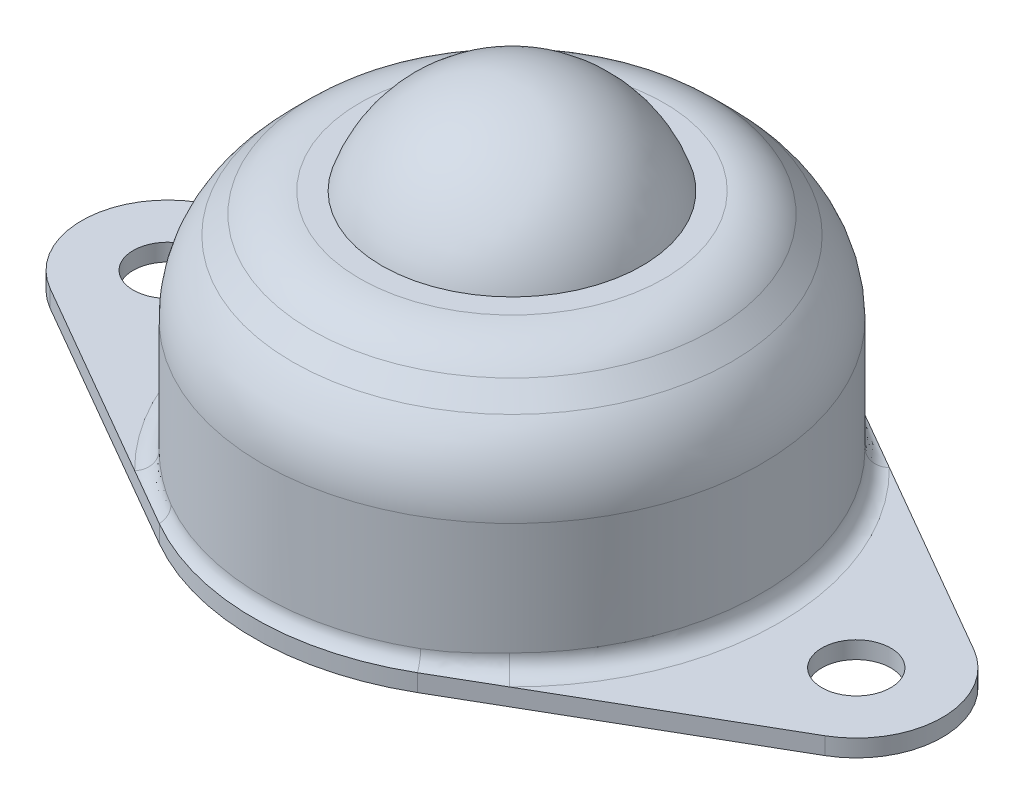
SolidWorks part; units mm, degrees
ref_plane "前视基准面" through (0, 0, 0) normal (0, 0, 1) x (1, 0, 0)
ref_plane "上视基准面" through (0, 0, 0) normal (0, 1, 0) x (1, 0, 0)
ref_plane "右视基准面" through (0, 0, 0) normal (1, 0, 0) x (0, 0, -1)
sketch "草图1" plane through (0, 0, 0) normal (0, 1, 0) x (1, 0, 0)
  line L0 (0, -26.7962) -> (0, 26.7962) construction
  line L1 (-22.5, 4.3301) -> (-7.5, 12.9904)
  line L2 (-22.5, -4.3301) -> (-7.5, -12.9904)
  line L3 (22.5, 4.3301) -> (7.5, 12.9904)
  line L4 (22.5, -4.3301) -> (7.5, -12.9904)
  circle A0 centre (0, 0) radius 15
  circle A1 centre (-20, 0) radius 2
  circle A2 centre (-20, 0) radius 5
  circle A3 centre (20, 0) radius 5
  circle A4 centre (20, 0) radius 2
  dimension "D1" = 4
  dimension "D3" = 30
  dimension "D4" = 10
  dimension "D2" = 20
extrude "凸台-拉伸1" add sketch "草图1" along normal blind 1 contours A2 A1 | A2 A0 L1 | A2 L2 A0 | A0 | A0 A3 L3 | L4 A3 A0 | A3 A4 region at (-15.4261, 0, -6.4178) region at (-17.5707, 0, -4.2077) region at (0, 0, 0) region at (-15.4261, 0, 6.4178) region at (15.4261, 0, -6.4178) region at (24.2077, 0, -2.4293) region at (15.4261, 0, 6.4178)
sketch "草图2" plane through (0, 1, 0) normal (0, 1, 0) x (1, 0, 0)
  circle A0 centre (0, 0) radius 14.5
  dimension "D1" = 29
extrude "凸台-拉伸2" add sketch "草图2" along normal blind 14
sketch "草图3" plane through (0, 0, 0) normal (0, 0, 1) x (1, 0, 0)
  line L0 (14.5, 15) -> (-14.5, 15) construction
  line L1 (0, 4.62) -> (0, 20.5)
  arc A0 (0, 20.5) -> (0, 4.62) centre (0, 12.56) ccw
  dimension "D1" = 15.88
  dimension "D2" = 2.44
revolve "旋转3" add sketch "草图3" angle 360 about L1
fillet "圆角1" radius 4 1 edges at (0, 15, 14.5) profile chamfer
fillet "圆角2" radius 6 1 edges at (0, 11, 14.5)
fillet "圆角3" radius 4 1 edges at (0, 15, 10.5)
fillet "圆角4" radius 1 1 edges at (0, 1, 14.5)
